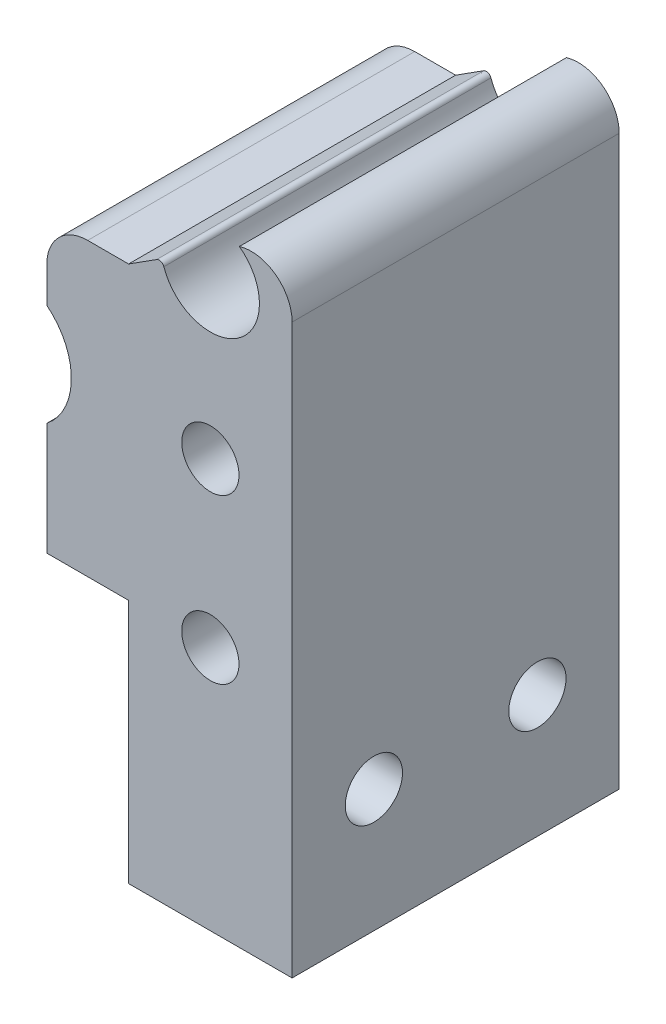
SolidWorks part; units mm, degrees
material "ABS"
ref_plane "Front Plane" through (0, 0, 0) normal (0, 0, 1) x (1, 0, 0)
ref_plane "Top Plane" through (0, 0, 0) normal (0, 1, 0) x (1, 0, 0)
ref_plane "Right Plane" through (0, 0, 0) normal (1, 0, 0) x (0, 0, -1)
sketch "Sketch2" plane through (0, 0, 0) normal (0, 0, 1) x (1, 0, 0)
  line L0 (0, 0) -> (0, 15)
  line L1 (0, 32.8146) -> (10, 39.1854)
  line L2 (0, 24.91) -> (0, 38.1505) construction
  line L3 (0, 15) -> (0, 32.8146) construction
  line L4 (10, 39.1854) -> (10, 0)
  line L5 (10, 0) -> (0, 0)
  line L6 (0, 32.8146) -> (-5, 32.8146)
  line L7 (0, 32.8146) -> (0, 15) construction
  line L8 (0, 15) -> (-5, 15)
  line L9 (-5, 32.8146) -> (-5, 15)
  point P4 (5, 36)
  dimension "D4" = 5
  dimension "D5" = 21
  dimension "D1" = 15
  dimension "D2" = 57.5
  dimension "D3" = 10
extrude "Boss-Extrude1" add sketch "Sketch2" along normal blind 20 contours L1 L0 L5 L4 region at (3.6306, 19.2094, 0)
sketch "Sketch3" plane through (10, 0, 0) normal (1, 0, 0) x (0, 0, -1)
  line L0 (-20, 7.5) -> (0, 7.5) construction
  line L1 (-20, 39.1854) -> (-20, 0) construction
  line L2 (0, 39.1854) -> (0, 0) construction
  line L3 (-20, 0) -> (0, 0) construction
  line L4 (-10, 7.5) -> (-10, 0) construction
  circle A0 centre (-15, 7.5) radius 1.75
  circle A1 centre (-5, 7.5) radius 1.75
  dimension "D2" = 3.5
  dimension "D3" = 3.5
  dimension "D1" = 7.5
  dimension "D4" = 5
  dimension "D5" = 5
extrude "Cut-Extrude1" cut sketch "Sketch3" against normal through all
sketch "Sketch4" plane through (0, 0, 20) normal (0, 0, 1) x (1, 0, 0)
  line L0 (0, 15) -> (-5, 15) construction
  line L1 (0, 0) -> (0, 15) construction
  line L2 (5, 0) -> (5, 25) construction
  line L4 (10, 0) -> (0, 0) construction
  circle A0 centre (5, 34.71) radius 3
  circle A1 centre (5, 25) radius 1.75
  circle A2 centre (-7.5, 25) radius 4
  circle A3 centre (5, 15) radius 1.75
  dimension "D1" = 6
  dimension "D2" = 19.71
  dimension "D3" = 5
  dimension "D4" = 3.5
  dimension "D5" = 25
  dimension "D6" = 8
  dimension "D7" = 7.5
  dimension "D8" = 15
extrude "Cut-Extrude2" cut sketch "Sketch4" against normal through all
fillet "Fillet2" radius 2.5 2 edges at (10, 39.1854, 10) (-5, 32.8146, 10)
fillet "Fillet3" radius 0.3 1 edges at (2.0575, 34.1254, 10)
